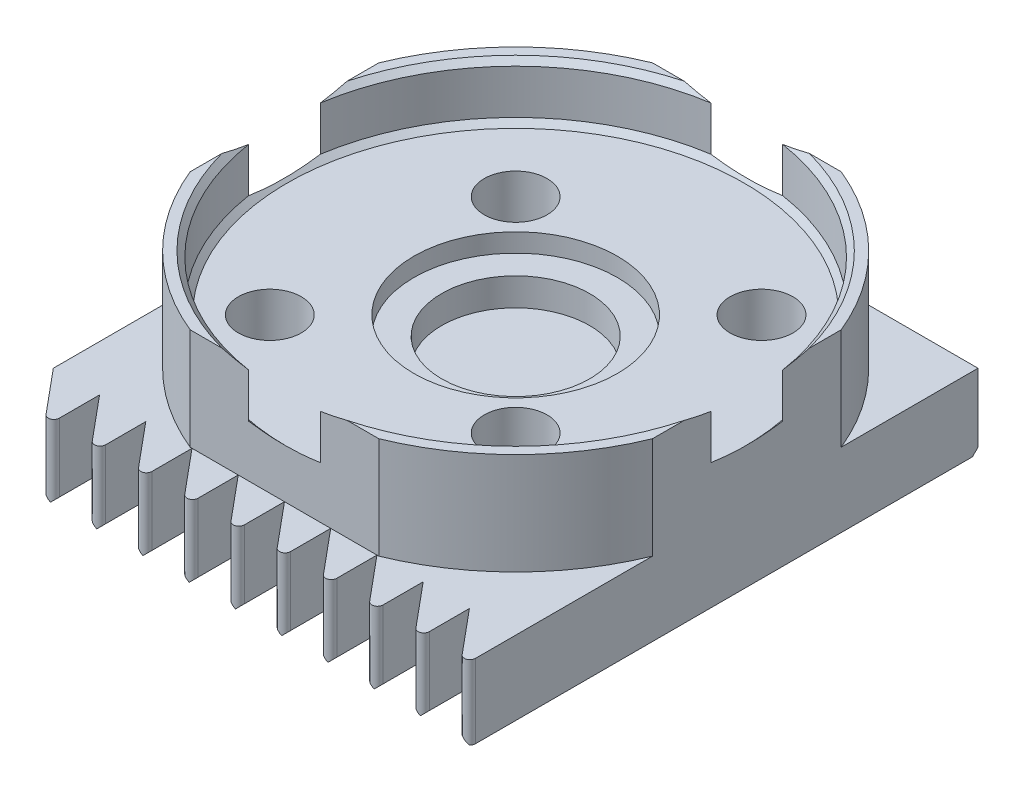
SolidWorks part; units mm, degrees
ref_plane "Front Plane" through (0, 0, 0) normal (0, 0, 1) x (1, 0, 0)
ref_plane "Top Plane" through (0, 0, 0) normal (0, 1, 0) x (1, 0, 0)
ref_plane "Right Plane" through (0, 0, 0) normal (1, 0, 0) x (0, 0, -1)
sketch "Sketch1" plane through (0, 0, 0) normal (0, 1, 0) x (1, 0, 0)
  line L0 (-6.6468, -6.6468) -> (6.6468, 6.6468) construction
  line L1 (-5.5331, 5.5331) -> (5.5331, -5.5331) construction
  line L2 (0, 0) -> (0, 3.1277) construction
  circle A0 centre (0, 0) radius 13.5
  circle A1 centre (0, 0) radius 5.5
  circle A2 centre (0, 0) radius 7.825 construction
  circle A3 centre (-5.5331, 5.5331) radius 1.7
  circle A4 centre (5.5331, -5.5331) radius 1.7
  circle A5 centre (0, 0) radius 9.4 construction
  circle A6 centre (-6.6468, -6.6468) radius 1.7
  circle A7 centre (6.6468, 6.6468) radius 1.7
  dimension "D1" = 27
  dimension "D2" = 11
  dimension "D3" = 15.65
  dimension "D4" = 18.8
  dimension "D5" = 3.4
  dimension "D6" = 45
extrude "Boss-Extrude1" add sketch "Sketch1" along normal blind 2.5 contours A0 A7 A6 A4 A3 A1 region at (-13.1182, 0, 0)
sketch "Sketch2" plane through (0, 2.5, 0) normal (0, 1, 0) x (1, 0, 0)
  circle A0 centre (0, 0) radius 12.65
  circle M6 centre (0, 0) radius 13.5
extrude "Boss-Extrude2" add sketch "Sketch2" along normal blind 3 contours A0 M6 region at (-13.1182, 2.5, 0)
sketch "Sketch3" plane through (0, 0, 0) normal (0, -1, 0) x (1, 0, 0)
  line L1 (12.5, -12.5) -> (-12.5, -12.5)
  line L2 (12.5, -12.5) -> (12.5, 12.5)
  line L3 (12.5, 12.5) -> (-12.5, 12.5)
  line L4 (-12.5, -12.5) -> (-12.5, 12.5)
  line L5 (12.5, -12.5) -> (-12.5, 12.5) construction
  line L6 (12.5, 12.5) -> (-12.5, -12.5) construction
  circle A0 centre (-5.5331, -5.5331) radius 1.7 construction
  circle A1 centre (6.6468, -6.6468) radius 1.7 construction
  circle A2 centre (5.5331, 5.5331) radius 1.7 construction
  circle A3 centre (-6.6468, 6.6468) radius 1.7 construction
  circle A4 centre (-5.5331, -5.5331) radius 1.7 construction
  circle A5 centre (6.6468, -6.6468) radius 1.7 construction
  circle A6 centre (5.5331, 5.5331) radius 1.7 construction
  circle A7 centre (-6.6468, 6.6468) radius 1.7 construction
  circle A8 centre (-6.6468, 6.6468) radius 3
  circle A9 centre (5.5331, 5.5331) radius 3
  circle A10 centre (6.6468, -6.6468) radius 3
  circle A11 centre (-5.5331, -5.5331) radius 3
  point P0 (0, 0)
  circle M5 centre (0, 0) radius 5.5
  circle M6 centre (0, 0) radius 13.5
  dimension "D1" = 6
  dimension "D2" = 25
extrude "Boss-Extrude3" add sketch "Sketch3" along normal blind 4 contours L4 L1 L2 L3 A11 A9 A10 A8 M6 M5 | L4 L3 M6 | L4 L1 M6 | L1 L2 M6 | L2 L3 M6 | A11 A9 M5 region at (10.3804, 0, -10.3804) region at (0, 0, -12.1464) region at (-10.3804, 0, -10.3804) region at (10.3804, 0, 10.3804) region at (-10.3804, 0, 10.3804) region at (0, 0, 0)
chamfer "Chamfer2" distance 0.3 angle 45 1 edges at (0, 2.5, 12.65)
sketch "Sketch4" plane through (0, 0, 0) normal (0, 1, 0) x (1, 0, 0)
  circle A0 centre (0, 0) radius 5.5 construction
  circle A1 centre (0, 0) radius 5.5
  circle A2 centre (0, 0) radius 4
  arc M1 (2.6146, -4.8388) -> (4.8388, -2.6146) centre (5.5331, -5.5331) cw
  arc M2 (4.8388, -2.6146) -> (-2.6146, 4.8388) centre (0, 0) ccw
  arc M3 (-2.6146, 4.8388) -> (-4.8388, 2.6146) centre (-5.5331, 5.5331) cw
  arc M4 (-4.8388, 2.6146) -> (2.6146, -4.8388) centre (0, 0) ccw
  dimension "D1" = 8
extrude "Boss-Extrude4" add sketch "Sketch4" along normal blind 1.5 contours A2 M4 M1 M2 M3 | A1 M3 | A1 M1 region at (5.1813, 0, 1.3103) region at (-3.6647, 0, -3.6647) region at (3.6647, 0, 3.6647)
sketch "Sketch6" plane through (0, 0, 0) normal (0, -1, 0) x (1, 0, 0)
  line L0 (5.099, -12.5) -> (-5.099, -12.5) construction
  line L1 (12.5, 5.099) -> (12.5, -5.099) construction
  line L2 (-5.099, 12.5) -> (5.099, 12.5) construction
  line L3 (-12.5, -5.099) -> (-12.5, 5.099) construction
  line L4 (5.099, -12.5) -> (-5.099, -12.5)
  line L5 (12.5, 5.099) -> (12.5, -5.099)
  line L6 (-5.099, 12.5) -> (5.099, 12.5)
  line L7 (-12.5, -5.099) -> (-12.5, 5.099)
  arc A0 (-5.099, -12.5) -> (5.099, -12.5) centre (0, 0) ccw construction
  arc A1 (12.5, -5.099) -> (12.5, 5.099) centre (0, 0) ccw construction
  arc A2 (5.099, 12.5) -> (-5.099, 12.5) centre (0, 0) ccw construction
  arc A3 (-12.5, 5.099) -> (-12.5, -5.099) centre (0, 0) ccw construction
  arc A4 (-5.099, -12.5) -> (5.099, -12.5) centre (0, 0) ccw
  arc A5 (12.5, -5.099) -> (12.5, 5.099) centre (0, 0) ccw
  arc A6 (5.099, 12.5) -> (-5.099, 12.5) centre (0, 0) ccw
  arc A7 (-12.5, 5.099) -> (-12.5, -5.099) centre (0, 0) ccw
extrude "Cut-Extrude1" cut sketch "Sketch6" against normal through all
chamfer "Chamfer3" distance 0.3 angle 45 4 edges at (8.9449, 5.5, -8.9449) (-8.9449, 5.5, -8.9449) (-8.9449, 5.5, 8.9449) (8.9449, 5.5, 8.9449)
sketch "Sketch7" plane through (0, -4, 0) normal (0, -1, 0) x (1, 0, 0)
  line L0 (12.5, 12.5) -> (-12.5, 12.5) construction
  line L1 (12.5, 12.5) -> (-12.5, 12.5)
  line L2 (-12.5, 12.5) -> (-10, 15.5)
  line L3 (-10, 15.5) -> (-10, 12.5)
  line L4 (-7.5, 15.5) -> (-7.5, 12.5)
  line L5 (-10, 12.5) -> (-7.5, 15.5)
  line L6 (-5, 15.5) -> (-5, 12.5)
  line L7 (-7.5, 12.5) -> (-5, 15.5)
  line L8 (-2.5, 15.5) -> (-2.5, 12.5)
  line L9 (-5, 12.5) -> (-2.5, 15.5)
  line L10 (0, 15.5) -> (0, 12.5)
  line L11 (-2.5, 12.5) -> (0, 15.5)
  line L12 (2.5, 15.5) -> (2.5, 12.5)
  line L13 (0, 12.5) -> (2.5, 15.5)
  line L14 (5, 15.5) -> (5, 12.5)
  line L15 (2.5, 12.5) -> (5, 15.5)
  line L16 (7.5, 15.5) -> (7.5, 12.5)
  line L17 (5, 12.5) -> (7.5, 15.5)
  line L18 (10, 15.5) -> (10, 12.5)
  line L19 (7.5, 12.5) -> (10, 15.5)
  line L20 (12.5, 15.5) -> (12.5, 12.5)
  line L21 (10, 12.5) -> (12.5, 15.5)
  line M9 (12.5, 12.5) -> (-12.5, 12.5)
  dimension "D1" = 3
  dimension "D2" = 2.5
  dimension "D3" = 10
extrude "Boss-Extrude5" add sketch "Sketch7" against normal up to surface (4 mm away) contours L3 L2 L1 | L5 L1 L4 | L7 L1 L6 | L9 L1 L8 | L11 L1 L10 | L13 L1 L12 | L15 L1 L14 | L17 L1 L16 | L19 L1 L18 | L21 L20 M9 region at (-10.8333, -4, 13.5) region at (-8.3333, -4, 13.5) region at (-5.8333, -4, 13.5) region at (-3.3333, -4, 13.5) region at (-0.8333, -4, 13.5) region at (1.6667, -4, 13.5) region at (4.1667, -4, 13.5) region at (6.6667, -4, 13.5) region at (9.1667, -4, 13.5) region at (11.6667, -4, 13.5) up to face at (5.5331, 0, 7.2331)
chamfer "Chamfer4" distance 0.3 angle 45 20 edges at (0, -4, -12.5) (11.25, -4, 14) (10, -4, 14) (8.75, -4, 14) (7.5, -4, 14) (6.25, -4, 14) (5, -4, 14) (3.75, -4, 14) (2.5, -4, 14) (1.25, -4, 14) (0, -4, 14) (-1.25, -4, 14) (-2.5, -4, 14) (-3.75, -4, 14) (-5, -4, 14) (-6.25, -4, 14) (-7.5, -4, 14) (-8.75, -4, 14) (-10, -4, 14) (-11.25, -4, 14)
fillet "Fillet1" radius 0.3 10 edges at (10, -1.85, 15.5) (7.5, -1.85, 15.5) (5, -1.85, 15.5) (2.5, -1.85, 15.5) (0, -1.85, 15.5) (-2.5, -1.85, 15.5) (-5, -1.85, 15.5) (-7.5, -1.85, 15.5) (-10, -1.85, 15.5) (12.5, -1.85, 15.5)
sketch "Sketch8" plane through (0, -4, 0) normal (0, -1, 0) x (1, 0, 0)
  line L0 (0, -6) -> (0, 6) construction
  circle A0 centre (0, 6) radius 1.2
  circle A1 centre (0, -6) radius 1.2
  dimension "D1" = 6
  dimension "D2" = 2.4
extrude "Cut-Extrude2" cut sketch "Sketch8" against normal blind 3
chamfer "Chamfer5" distance 2 angle 45 4 edges at (6.6468, 0, -9.6468) (-5.5331, 0, -8.5331) (5.5331, 0, 2.5331) (-6.6468, 0, 3.6468)
